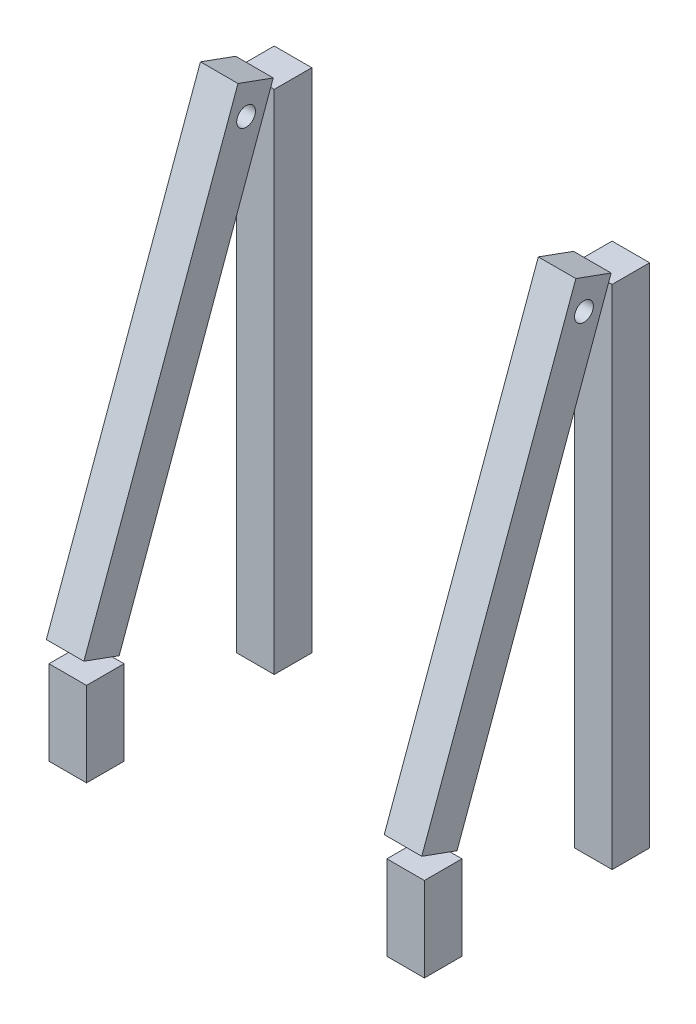
SolidWorks part; units mm, degrees
ref_plane "Front Plane" through (0, 0, 0) normal (0, 0, 1) x (1, 0, 0)
ref_plane "Top Plane" through (0, 0, 0) normal (0, 1, 0) x (1, 0, 0)
ref_plane "Right Plane" through (0, 0, 0) normal (1, 0, 0) x (0, 0, -1)
sketch "Sketch1" plane through (0, 0, 0) normal (0, 1, 0) x (1, 0, 0)
  line L1 (203.2, 139.7) -> (254, 139.7)
  line L2 (203.2, 139.7) -> (203.2, 88.9)
  line L3 (203.2, 88.9) -> (254, 88.9)
  line L4 (254, 139.7) -> (254, 88.9)
  line L5 (203.2, -114.3) -> (254, -114.3)
  line L6 (203.2, -114.3) -> (203.2, -165.1)
  line L7 (203.2, -165.1) -> (254, -165.1)
  line L8 (254, -114.3) -> (254, -165.1)
  line L9 (-254, 139.7) -> (-203.2, 139.7)
  line L10 (-254, 139.7) -> (-254, 88.9)
  line L11 (-254, 88.9) -> (-203.2, 88.9)
  line L12 (-203.2, 139.7) -> (-203.2, 88.9)
  line L13 (-254, -114.3) -> (-203.2, -114.3)
  line L14 (-254, -114.3) -> (-254, -165.1)
  line L15 (-254, -165.1) -> (-203.2, -165.1)
  line L16 (-203.2, -114.3) -> (-203.2, -165.1)
  dimension "D1" = 50.8
  dimension "D2" = 88.9
  dimension "D3" = 114.3
  dimension "D4" = 203.2
  dimension "D5" = 203.2
extrude "Boss-Extrude1" add sketch "Sketch1" along normal blind 114.3
sketch "Sketch2" plane through (0, 114.3, 0) normal (0, 1, 0) x (1, 0, 0)
  line L0 (203.2, 139.7) -> (203.2, 88.9) construction
  line L1 (203.2, 88.9) -> (254, 88.9) construction
  line L2 (254, 88.9) -> (254, 139.7) construction
  line L3 (254, 139.7) -> (203.2, 139.7) construction
  line L4 (-254, 139.7) -> (-254, 88.9) construction
  line L5 (-254, 88.9) -> (-203.2, 88.9) construction
  line L6 (-203.2, 88.9) -> (-203.2, 139.7) construction
  line L7 (-203.2, 139.7) -> (-254, 139.7) construction
  line L8 (203.2, 139.7) -> (203.2, 88.9)
  line L9 (203.2, 88.9) -> (254, 88.9)
  line L10 (254, 88.9) -> (254, 139.7)
  line L11 (254, 139.7) -> (203.2, 139.7)
  line L12 (-254, 139.7) -> (-254, 88.9)
  line L13 (-254, 88.9) -> (-203.2, 88.9)
  line L14 (-203.2, 88.9) -> (-203.2, 139.7)
  line L15 (-203.2, 139.7) -> (-254, 139.7)
extrude "Boss-Extrude2" add sketch "Sketch2" along normal blind 571.5
sketch "Sketch3" plane through (254, 0, 0) normal (1, 0, 0) x (0, 0, -1)
  line L0 (-168.6704, 144.3746) -> (-120.934, 127)
  line L1 (-168.6704, 144.3746) -> (39.8251, 717.2112)
  line L2 (-120.934, 127) -> (87.5614, 699.8366)
  line L3 (39.8251, 717.2112) -> (87.5614, 699.8366)
  line L4 (-165.1, 0) -> (-114.3, 0)
  line L5 (-114.3, 0) -> (-114.3, 114.3)
  line L6 (-114.3, 114.3) -> (-165.1, 114.3)
  line L7 (-165.1, 114.3) -> (-165.1, 0)
  line L8 (-165.1, 0) -> (-114.3, 0)
  line L9 (-114.3, 0) -> (-114.3, 114.3)
  line L10 (-114.3, 114.3) -> (-165.1, 114.3)
  line L11 (-165.1, 114.3) -> (-165.1, 0)
  circle A0 centre (50.8, 673.1) radius 12.7
  point P10 (85.9011, 699.8366)
  dimension "D9" = 25.4
  dimension "D2" = 50.8
  dimension "D3" = 609.6
  dimension "D4" = 20
  dimension "D5" = 12.7
  dimension "D6" = 50.8
  dimension "D7" = 25.4
  dimension "D8" = 673.1
  dimension "D1" = 0
extrude "Boss-Extrude3" add sketch "Sketch3" along direction (-1, 0, 0) on the side against the normal blind 50.8 separate body contours L3 L1 L0 L2 A0 region at (254, 417.9304, 42.0741)
extrude "Boss-Extrude4" add sketch "Sketch3<3>" against normal blind 50.8 from surface separate body contours L3 L1 L0 L2 A0 region at (254, 417.9304, 42.0741) starting at face at (-203.2, 57.15, 139.7)
sketch "Sketch3<3>" plane through (254, 0, 0) normal (1, 0, 0) x (0, 0, -1) same geometry as "Sketch3"
